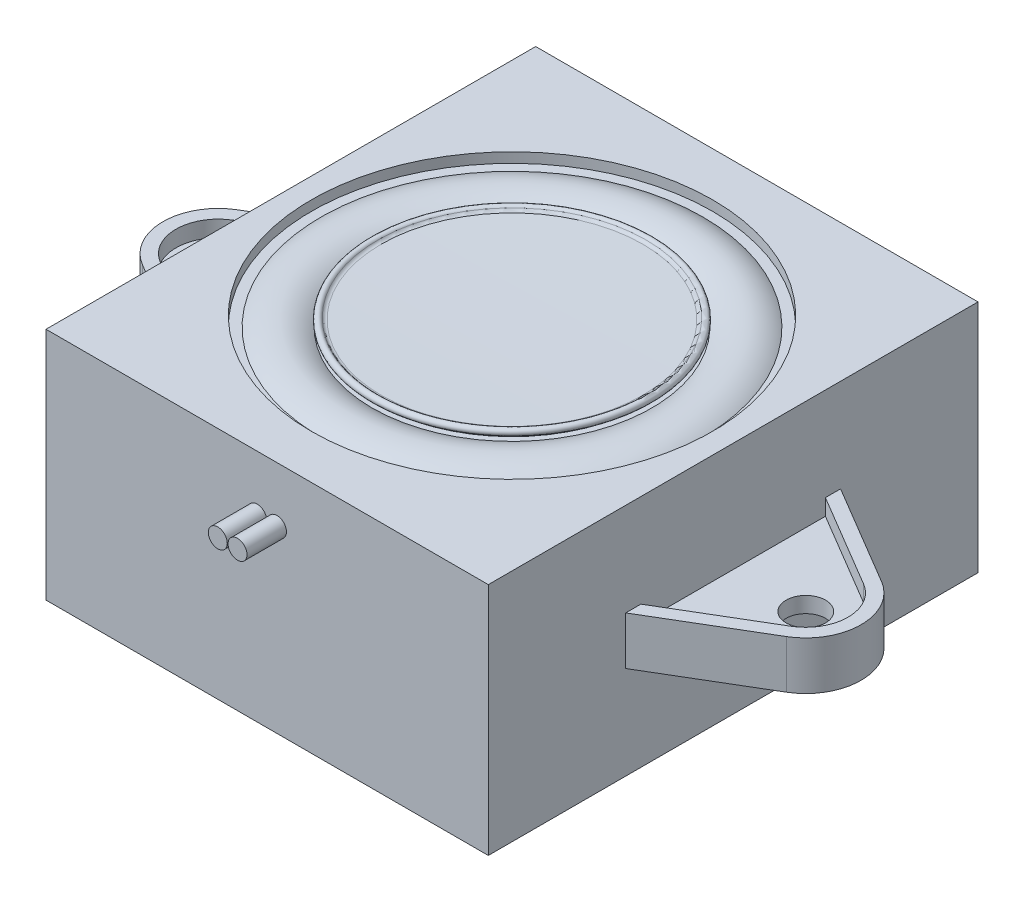
SolidWorks part; units mm, degrees
material "ABS"
ref_plane "Front Plane" through (0, 0, 0) normal (0, 0, 1) x (1, 0, 0)
ref_plane "Top Plane" through (0, 0, 0) normal (0, 1, 0) x (1, 0, 0)
ref_plane "Right Plane" through (0, 0, 0) normal (1, 0, 0) x (0, 0, -1)
sketch "Sketch1" plane through (0, 0, 0) normal (0, 1, 0) x (1, 0, 0)
  line L1 (0, 0) -> (28, 0)
  line L2 (0, 0) -> (0, 31)
  line L3 (0, 31) -> (28, 31)
  line L4 (28, 0) -> (28, 31)
  dimension "D1" = 31
  dimension "D2" = 28
extrude "Boss-Extrude1" add sketch "Sketch1" along normal mid plane 14.85
sketch "Sketch2" plane through (0, 0, 0) normal (0, 1, 0) x (1, 0, 0)
  line L0 (14, 0) -> (14, 31) construction
  line L1 (0, 0) -> (28, 0) construction
  line L2 (28, 31) -> (0, 31) construction
  line L3 (0, 8.7) -> (0, 22.3)
  line L4 (0, 31) -> (0, 0) construction
  line L5 (-6.3863, 18.5098) -> (0, 22.3)
  line L6 (-6.3863, 12.4902) -> (0, 8.7)
  line L7 (34.3863, 12.4902) -> (28, 8.7)
  line L8 (34.3863, 18.5098) -> (28, 22.3)
  line L9 (28, 8.7) -> (28, 22.3)
  circle A0 centre (-4.6, 15.5) radius 1.25
  arc A1 (-6.3863, 18.5098) -> (-6.3863, 12.4902) centre (-4.6, 15.5) ccw
  arc A2 (34.3863, 18.5098) -> (34.3863, 12.4902) centre (32.6, 15.5) cw
  circle A3 centre (32.6, 15.5) radius 1.25
  point P8 (-8.1, 15.5)
  point P9 (14, 15.5)
  point P16 (0, 15.5)
  point P17 (-3.35, 15.5)
  point P25 (31.35, 15.5)
  point P26 (28, 15.5)
  dimension "D1" = 2.5
  dimension "D3" = 8.1
  dimension "D2" = 13.6
  dimension "D4" = 34.7
extrude "Boss-Extrude2" add sketch "Sketch2" along normal mid plane 1
sketch "Sketch5" plane through (0, 0, 0) normal (0, 1, 0) x (1, 0, 0)
  line L0 (-6.3863, 12.4902) -> (0, 8.7) construction
  line L2 (0, 22.3) -> (-6.3863, 18.5098) construction
  line L3 (34.3863, 18.5098) -> (28, 22.3) construction
  line L4 (28, 22.3) -> (28, 8.7) construction
  line L5 (28, 8.7) -> (34.3863, 12.4902) construction
  line L6 (-6.3863, 12.4902) -> (0, 8.7)
  line L8 (0, 22.3) -> (-6.3863, 18.5098)
  line L9 (34.3863, 18.5098) -> (28, 22.3)
  line L10 (28, 22.3) -> (28, 8.7)
  line L11 (28, 8.7) -> (34.3863, 12.4902)
  line L12 (-5.965, 13.2) -> (-0.8255, 10.1499)
  line L13 (-0.8255, 10.1499) -> (-0.8255, 20.8501)
  line L14 (-0.8255, 20.8501) -> (-5.965, 17.8)
  line L15 (33.965, 17.8) -> (28.8255, 20.8501)
  line L16 (28.8255, 20.8501) -> (28.8255, 10.1499)
  line L17 (28.8255, 10.1499) -> (33.965, 13.2)
  line L18 (0, 8.7) -> (0, 22.3) construction
  line L19 (-0.8255, 20.8501) -> (0, 21.3401)
  line L20 (0, 31) -> (0, 0) construction
  line L21 (-0.8255, 10.1499) -> (0, 9.6599)
  line L22 (0, 8.7) -> (0, 22.3) construction
  line L23 (28.8255, 10.1499) -> (28, 9.6599)
  line L24 (28.8255, 20.8501) -> (28, 21.3401)
  line L26 (0, 22.3) -> (0, 8.7)
  arc A0 (-6.3863, 18.5098) -> (-6.3863, 12.4902) centre (-4.6, 15.5) ccw construction
  arc A1 (34.3863, 12.4902) -> (34.3863, 18.5098) centre (32.6, 15.5) ccw construction
  arc A2 (-6.3863, 18.5098) -> (-6.3863, 12.4902) centre (-4.6, 15.5) ccw
  arc A3 (34.3863, 12.4902) -> (34.3863, 18.5098) centre (32.6, 15.5) ccw
  arc A4 (-5.965, 17.8) -> (-5.965, 13.2) centre (-4.6, 15.5) ccw
  arc A5 (33.965, 13.2) -> (33.965, 17.8) centre (32.6, 15.5) ccw
  dimension "D1" = 0.8255
extrude "Boss-Extrude3" add sketch "Sketch5" along normal mid plane 3.05 contours A4 L14 L19 L26 L8 A2 L6 L21 L12 | A5 L17 L23 L10 L11 A3 L9 L24 L15 region at (-7.9417, 0, -15.5) region at (35.9417, 0, -15.5)
sketch "Sketch3" plane through (0, 7.425, 0) normal (0, 1, 0) x (1, 0, 0)
  line L0 (14, 0) -> (14, 31) construction
  circle A0 centre (14, 15.5) radius 12.7
  dimension "D1" = 25.4
extrude "Cut-Extrude1" cut sketch "Sketch3" against normal blind 0.635
ref_plane "Plane1" through (0, 0, -15.5) normal (0, 0, -1) x (-1, 0, 0)
sketch "Sketch6" plane through (0, 0, -15.5) normal (0, 0, -1) x (-1, 0, 0)
  line L0 (-22.4935, 6.79) -> (-22.8109, 7.0466)
  line L1 (-1.3, 6.79) -> (-26.7, 6.79) construction
  line L4 (-14, -7.425) -> (-14, 7.425) construction
  line L5 (-28, -7.425) -> (0, -7.425) construction
  line L6 (-28, 7.425) -> (0, 7.425) construction
  line L7 (-22.4935, 6.79) -> (-14, 6.79)
  line L8 (-26.0833, 6.79) -> (-22.86, 6.79)
  line L9 (-14, 7.1404) -> (-14, 6.79)
  line L10 (-14, 7.1404) -> (-13.1185, 7.1404) construction
  arc A0 (-22.8109, 7.0466) -> (-22.4946, 7.3216) centre (-22.6771, 7.2121) cw
  arc A2 (-22.86, 6.79) -> (-26.0833, 6.79) centre (-24.4717, 4.5829) ccw
  arc A3 (-22.2808, 7.1986) -> (-14, 7.1404) centre (-14, 595.9011) ccw
  arc A4 (-22.4946, 7.3216) -> (-22.2808, 7.1986) centre (-22.2773, 7.452) ccw
  point P22 (-22.89, 7.2121)
  dimension "D1" = 17.78
revolve "Revolve1" add sketch "Sketch6" angle 360 about L4
sketch "Sketch7" plane through (0, 0, 0) normal (0, 0, 1) x (1, 0, 0)
  line L0 (14, 3.925) -> (14, 7.425) construction
  line L2 (0, 7.425) -> (28, 7.425) construction
  line L3 (13.375, 3.925) -> (14.625, 3.925) construction
  circle A0 centre (14.625, 3.925) radius 0.6
  circle A1 centre (13.375, 3.925) radius 0.6
  point P8 (14, 3.925)
  dimension "D1" = 1.2
  dimension "D2" = 3.5
  dimension "D3" = 1.25
extrude "Boss-Extrude6" add sketch "Sketch7" along normal blind 2.5
